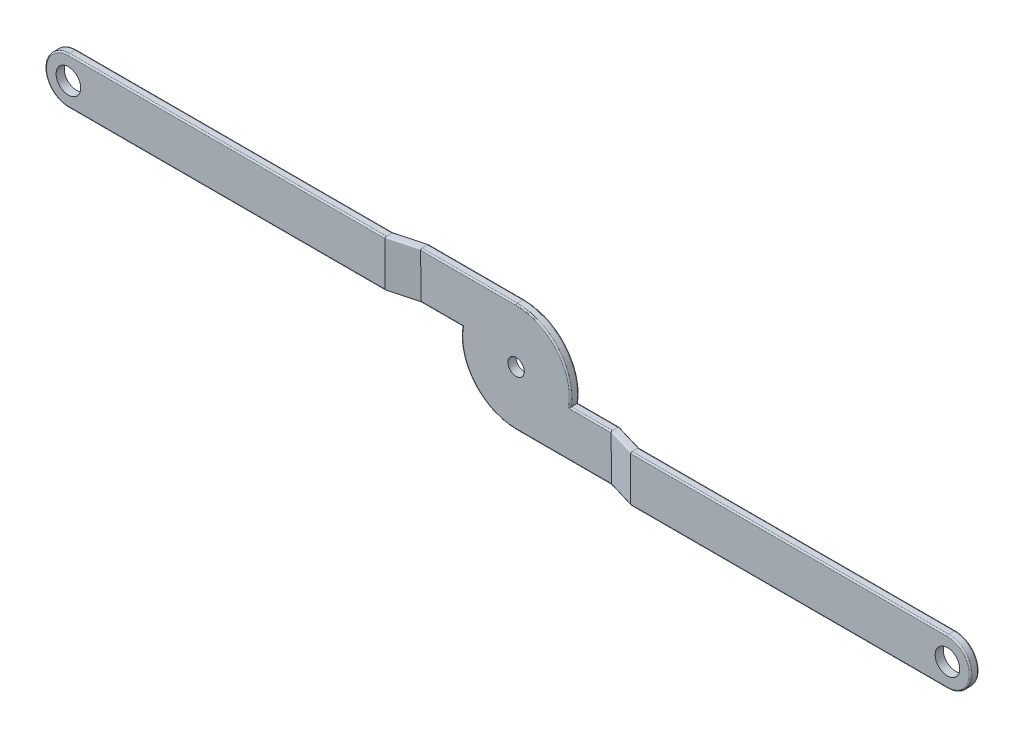
SolidWorks part; units mm, degrees
ref_plane "Front Plane" through (0, 0, 0) normal (0, 0, 1) x (1, 0, 0)
ref_plane "Top Plane" through (0, 0, 0) normal (0, 1, 0) x (1, 0, 0)
ref_plane "Right Plane" through (0, 0, 0) normal (1, 0, 0) x (0, 0, -1)
sketch "Sketch1" plane through (0, 0, 0) normal (0, 0, 1) x (1, 0, 0)
  line L0 (-1.5, 0) -> (1.5, 0) construction
  line L9 (0, 1.5) -> (0, -1.5) construction
  line L14 (-17.5, 10) -> (-17.3869, 1.5)
  line L15 (17.3869, -1.5) -> (17.5, -10)
  line L16 (-9.8869, 1.5) -> (-17.3869, 1.5)
  line L17 (-85, 5.751) -> (-85, 5.749)
  line L18 (0, 10) -> (-17.5, 10)
  line L19 (9.8869, -1.5) -> (17.3869, -1.5)
  line L20 (85, -5.751) -> (85, -5.749)
  line L21 (0, -10) -> (17.5, -10)
  line L22 (-17.5, 10) -> (-80.751, 10) construction
  line L23 (-17.3869, 1.5) -> (-80.751, 1.5) construction
  line L24 (17.5, -10) -> (80.751, -10) construction
  line L25 (17.3869, -1.5) -> (80.751, -1.5) construction
  circle A1 centre (0, 0) radius 1.5
  arc A9 (0, -10) -> (-9.8869, 1.5) centre (0, 0) cw
  arc A10 (-85, 5.749) -> (-80.751, 1.5) centre (-80.751, 5.749) ccw construction
  arc A11 (-80.751, 10) -> (-85, 5.751) centre (-80.751, 5.751) ccw construction
  arc A12 (0, 10) -> (9.8869, -1.5) centre (0, 0) cw
  arc A13 (85, -5.749) -> (80.751, -1.5) centre (80.751, -5.749) ccw construction
  arc A14 (85, -5.751) -> (80.751, -10) centre (80.751, -5.751) cw construction
  circle A15 centre (-80.751, 5.749) radius 1.5 construction
  circle A16 centre (80.751, -5.749) radius 1.5 construction
  point P7 (-17.3869, 1.5)
  point P9 (-17.5, 10)
  point P10 (17.3869, -1.5)
  point P11 (17.5, -10)
  dimension "D1" = 3
  dimension "D2" = 3
  dimension "D7" = 17.5
  dimension "D8" = 7.5
  dimension "D3" = 3
  dimension "D4" = 17.5
  dimension "D5" = 1.5
  dimension "D6" = 7.5
extrude "Boss-Extrude1" add sketch "Sketch1" against normal blind 1.5 contours A15 | A16 | A12 L18 L14 L16 A9 L21 L15 L19 A1
sketch "Sketch2" plane through (0, 0, 0) normal (0, 0, 1) x (1, 0, 0)
  line L1 (22.5, -1.5204) -> (80.5, -1.5204)
  line L2 (22.5, -1.5204) -> (22.5, -10.0204)
  line L3 (22.5, -10.0204) -> (80.5, -10.0204)
  line L4 (80.5, -1.5204) -> (80.5, -10.0204) construction
  line L5 (-22.5, 10.1202) -> (-80.5, 10.1202)
  line L6 (-22.5, 10.1202) -> (-22.5, 1.6202)
  line L7 (-22.5, 1.6202) -> (-80.5, 1.6202)
  line L8 (-80.5, 10.1202) -> (-80.5, 1.6202) construction
  arc A0 (-80.5, 10.1202) -> (-80.5, 1.6202) centre (-80.5, 5.8702) ccw
  arc A1 (80.5, -10.0204) -> (80.5, -1.5204) centre (80.5, -5.7704) ccw
  arc A2 (80.5, -1.5204) -> (80.5, -10.0204) centre (80.5, -5.7704) ccw construction
  arc A3 (-80.5, 1.6202) -> (-80.5, 10.1202) centre (-80.5, 5.8702) ccw construction
  circle A4 centre (-80.5, 5.8702) radius 2.25
  circle A5 centre (80.5, -5.7704) radius 2.25
  dimension "D7" = 4.5
  dimension "D8" = 4.5
  dimension "D1" = 22.5
  dimension "D2" = 22.5
  dimension "D3" = 8.5
  dimension "D4" = 8.5
  dimension "D5" = 58
  dimension "D6" = 58
extrude "Boss-Extrude2" add sketch "Sketch2" along normal blind 1.5 separate body
fillet "Fillet12" radius 0.25 6 edges at (51.5, -1.5204, 1.5) (84.75, -5.7704, 1.5) (51.5, -10.0204, 1.5) (51.5, -10.0204, 0) (84.75, -5.7704, 0) (51.5, -1.5204, 0)
fillet "Fillet13" radius 0.25 12 edges at (13.6369, -1.5, 0) (8.75, -10, 0) (-7.5829, -6.5192, 0) (-13.6369, 1.5, 0) (-8.75, 10, 0) (7.5829, 6.5192, 0) (-8.75, 10, -1.5) (-13.6369, 1.5, -1.5) (-7.5829, -6.5192, -1.5) (8.75, -10, -1.5) (13.6369, -1.5, -1.5) (7.5829, 6.5192, -1.5)
fillet "Fillet14" radius 0.25 6 edges at (-51.5, 10.1202, 0) (-84.75, 5.8702, 0) (-51.5, 1.6202, 0) (-51.5, 1.6202, 1.5) (-84.75, 5.8702, 1.5) (-51.5, 10.1202, 1.5)
loft "Loft3" add section face at (17.4434, -5.75, -0.75) section face at (22.5, -5.7704, 0.75)
loft "Loft4" add section face at (-17.4434, 5.75, -0.75) section face at (-22.5, 5.8702, 0.75)
